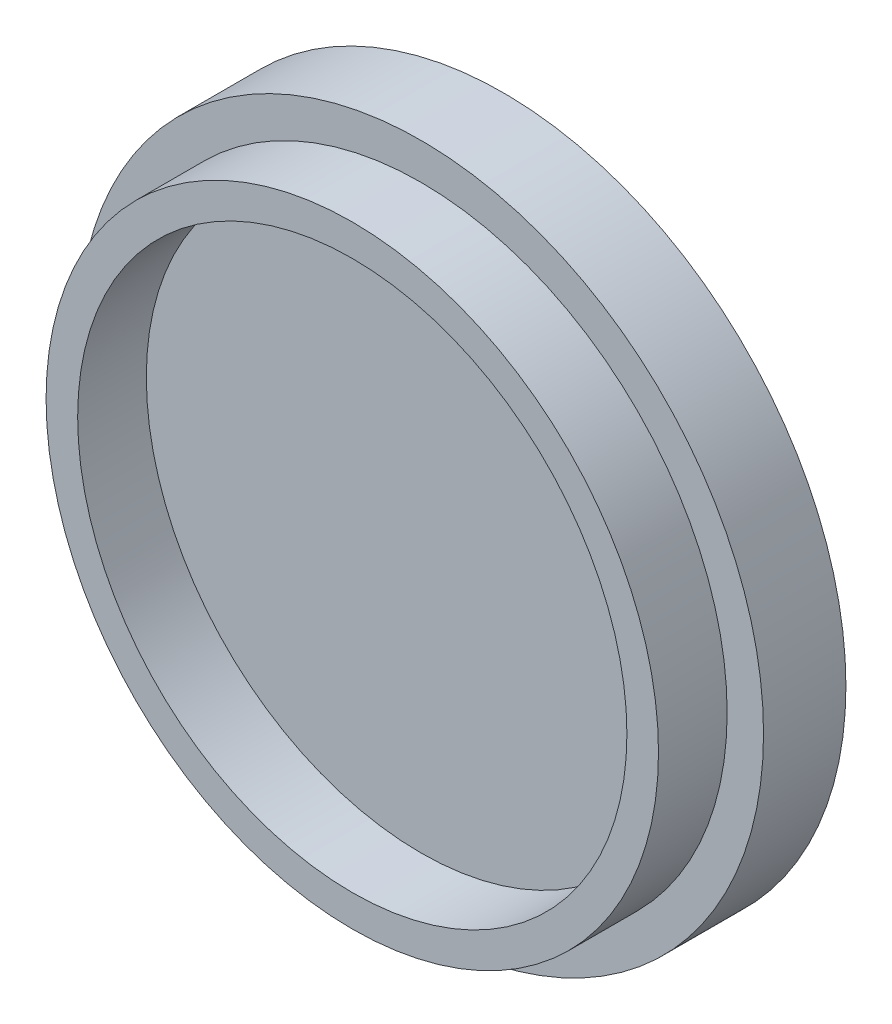
SolidWorks part; units mm, degrees
ref_plane "Front Plane" through (0, 0, 0) normal (0, 0, 1) x (1, 0, 0)
ref_plane "Top Plane" through (0, 0, 0) normal (0, 1, 0) x (1, 0, 0)
ref_plane "Right Plane" through (0, 0, 0) normal (1, 0, 0) x (0, 0, -1)
sketch "Sketch1" plane through (0, 0, 0) normal (0, 0, 1) x (1, 0, 0)
  circle A0 centre (0, 0) radius 24.95
extrude "Boss-Extrude1" add sketch "Sketch1" along normal blind 6
sketch "Sketch2" plane through (0, 0, 6) normal (0, 0, 1) x (1, 0, 0)
  circle A0 centre (0, 0) radius 22.3
  circle A1 centre (0, 0) radius 20
extrude "Boss-Extrude2" add sketch "Sketch2" along normal blind 5
